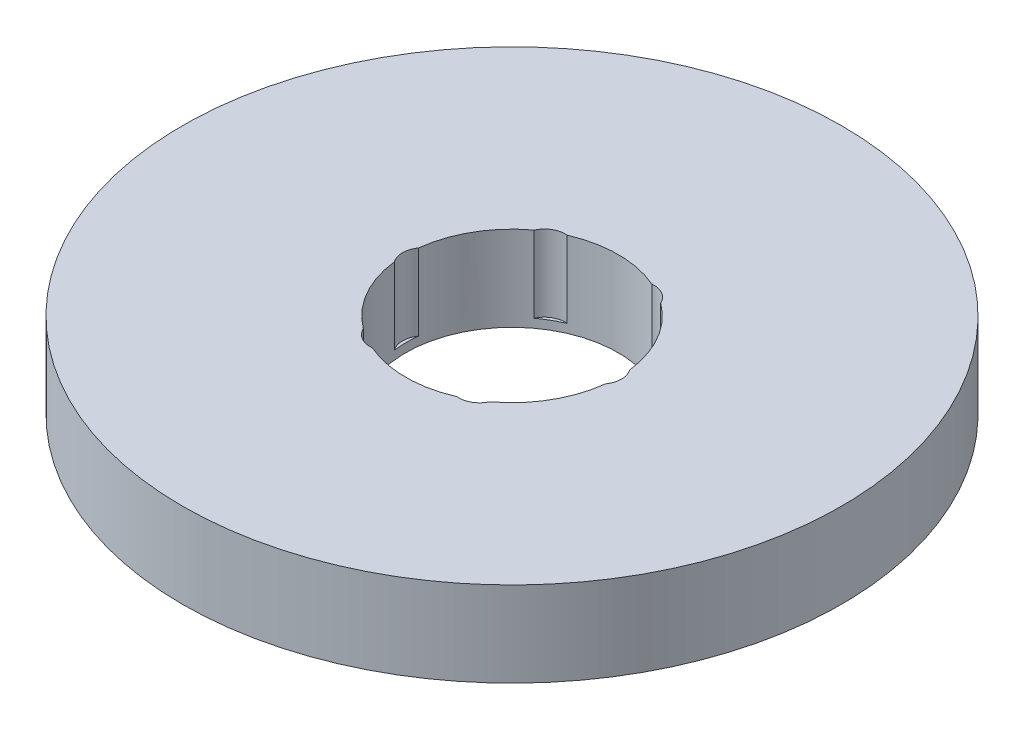
SolidWorks part; units mm, degrees
ref_plane "Front Plane" through (0, 0, 0) normal (0, 0, 1) x (1, 0, 0)
ref_plane "Top Plane" through (0, 0, 0) normal (0, 1, 0) x (1, 0, 0)
ref_plane "Right Plane" through (0, 0, 0) normal (1, 0, 0) x (0, 0, -1)
sketch "Sketch1" plane through (0, 0, 0) normal (0, 1, 0) x (1, 0, 0)
  circle A0 centre (0, 0) radius 77.5
  dimension "FLANGE_OD" = 155
extrude "Boss-Extrude1" add sketch "Sketch1" along normal blind 20
sketch "Sketch2" plane through (0, 0, 0) normal (0, 1, 0) x (1, 0, 0)
  circle A0 centre (0, 0) radius 25
  dimension "BORE_D" = 50
extrude "Cut-Extrude1" cut sketch "Sketch2" along normal through all
sketch "Sketch3" plane through (0, 20, 0) normal (0, 1, 0) x (1, 0, 0)
  circle A0 centre (0, 0) radius 20.8324 construction
  circle A1 centre (-20.8324, 0) radius 4.9137
  dimension "BOLT_D" = 9.8274
  dimension "BOLT_PCD" = 41.6648
extrude "Cut-Extrude2" cut sketch "Sketch3" against normal blind 17.9634
pattern_circular "CirPattern1" count 6 over 360 about axis through (0, 0, 0) along (0, 1, 0) of "Cut-Extrude2"
